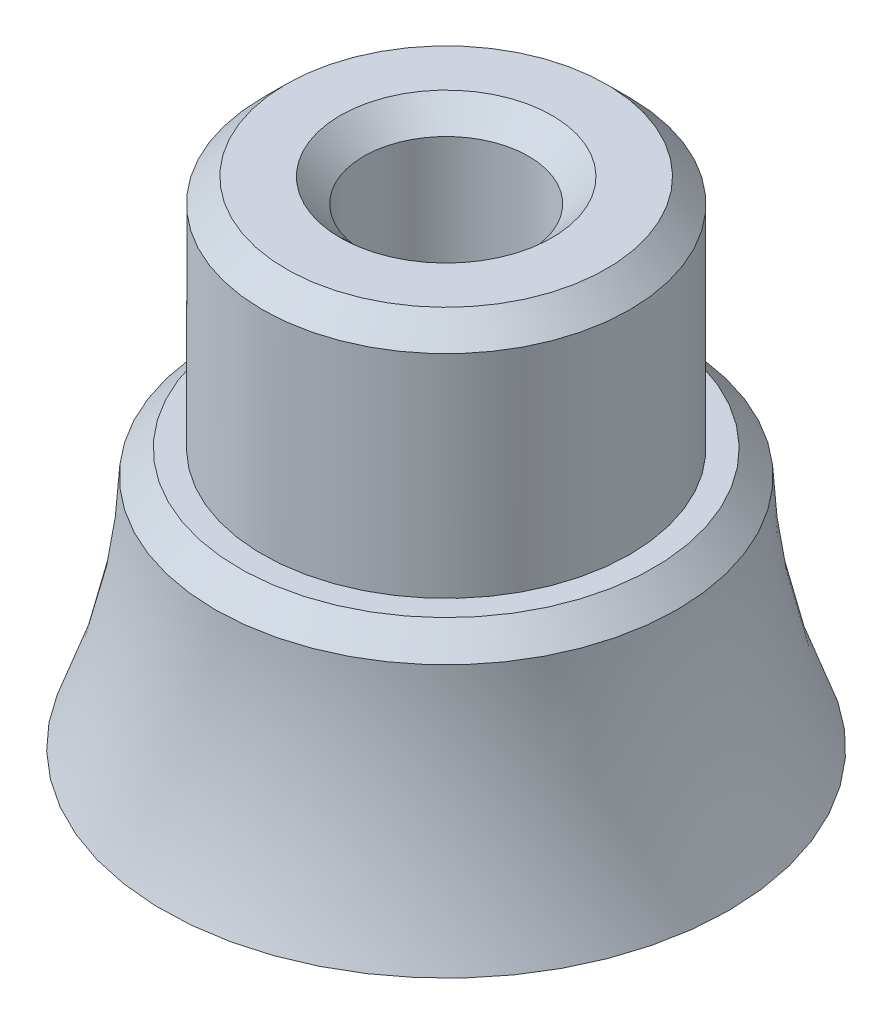
SolidWorks part; units mm, degrees
ref_plane "Front Plane" through (0, 0, 0) normal (0, 0, 1) x (1, 0, 0)
ref_plane "Top Plane" through (0, 0, 0) normal (0, 1, 0) x (1, 0, 0)
ref_plane "Right Plane" through (0, 0, 0) normal (1, 0, 0) x (0, 0, -1)
sketch "Sketch1" plane through (0, 0, 0) normal (0, 0, 1) x (1, 0, 0)
  line L0 (0, -1052.6268) -> (0, 51578.7139) construction
  line L1 (1.75, 0) -> (1.75, 10.5)
  line L2 (1.75, 10.5) -> (3.9, 10.5)
  line L3 (3.9, 10.5) -> (3.9, 5.5)
  line L4 (3.9, 5.5) -> (4.9, 5.5)
  line L5 (6, 0) -> (1.75, 0)
  arc A0 (4.9, 5.5) -> (6, 0) centre (19.2, 5.5) ccw
  point P10 (3.9, 8)
  dimension "D1" = 3.5
  dimension "D2" = 7.8
  dimension "D3" = 5
  dimension "D4" = 8
  dimension "D5" = 1
  dimension "D6" = 12
revolve "Revolve1" add sketch "Sketch1" angle 360 about L0
chamfer "Chamfer1" distance 0.5 angle 45 4 edges at (4.9, 5.5, 0) (1.75, 10.5, 0) (1.75, 0, 0) (3.9, 10.5, 0)
